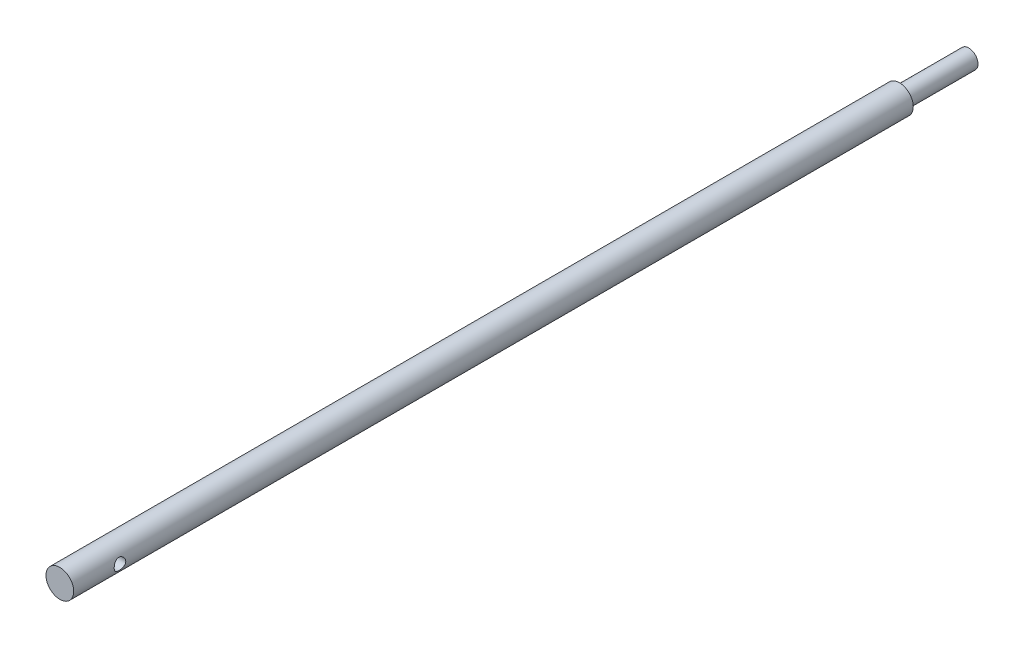
SolidWorks part; units mm, degrees
ref_plane "Front Plane" through (0, 0, 0) normal (0, 0, 1) x (1, 0, 0)
ref_plane "Top Plane" through (0, 0, 0) normal (0, 1, 0) x (1, 0, 0)
ref_plane "Right Plane" through (0, 0, 0) normal (1, 0, 0) x (0, 0, -1)
sketch "Sketch2" plane through (0, 0, 0) normal (0, 0, 1) x (1, 0, 0)
  circle A0 centre (0, 0) radius 3
  dimension "D1" = 6
extrude "Boss-Extrude1" add sketch "Sketch2" against normal blind 181.5
sketch "Sketch3" plane through (0, 0, -181.5) normal (0, 0, -1) x (-1, 0, 0)
  circle A0 centre (0, 0) radius 2
  circle A1 centre (0, 0) radius 3
  circle A2 centre (0, 0) radius 3 construction
  dimension "D1" = 1
sketch "Sketch6" plane through (0, 0, -181.5) normal (0, 0, -1) x (-1, 0, 0)
  circle A0 centre (0, 0) radius 2
  circle A1 centre (0, 0) radius 3 construction
  dimension "D1" = 1
extrude "Boss-Extrude3" add sketch "Sketch6" along normal blind 15
sketch "Sketch9" plane through (0, 0, 0) normal (1, 0, 0) x (0, 0, -1)
  line L0 (3.3, 0) -> (-3.3, 0) construction
  circle A0 centre (10, 0) radius 1.25
  dimension "D1" = 2.5
  dimension "D2" = 10
extrude "Cut-Extrude1" cut sketch "Sketch9" against normal through all both and the other way through all
